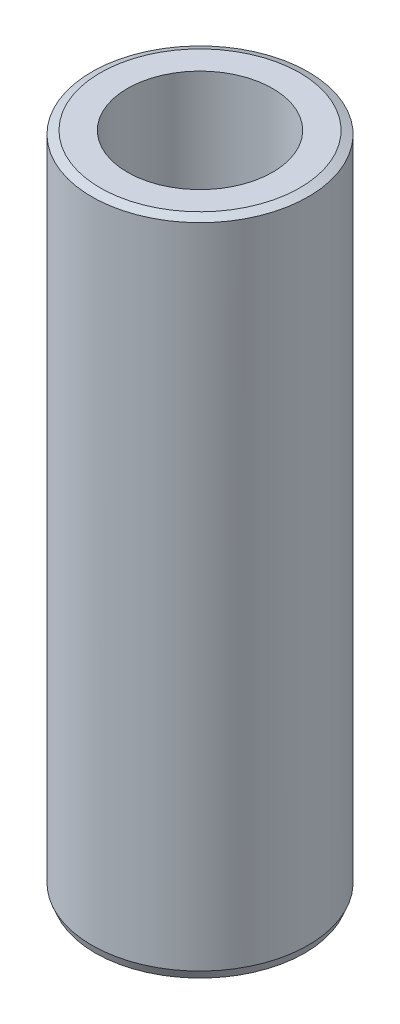
SolidWorks part; units mm, degrees
ref_plane "Front Plane" through (0, 0, 0) normal (0, 0, 1) x (1, 0, 0)
ref_plane "Top Plane" through (0, 0, 0) normal (0, 1, 0) x (1, 0, 0)
ref_plane "Right Plane" through (0, 0, 0) normal (1, 0, 0) x (0, 0, -1)
sketch "Sketch1" plane through (0, 0, 0) normal (0, 1, 0) x (1, 0, 0)
  circle A0 centre (0, 0) radius 60
  dimension "SHAFT_OD" = 120
extrude "Boss-Extrude1" add sketch "Sketch1" along normal blind 365.9122
sketch "Sketch2" plane through (0, 0, 0) normal (0, 1, 0) x (1, 0, 0)
  circle A0 centre (0, 0) radius 40.2621
  dimension "BORE_D" = 80.5243
extrude "Cut-Extrude1" cut sketch "Sketch2" along normal through all
chamfer "Chamfer1" distance 1.9017 angle 67.99 2 edges at (0, 365.9122, 60) (0, 0, 60) first distance on face at (0, 365.9122, 60) first distance on face at (0, 0, 40.2621)
